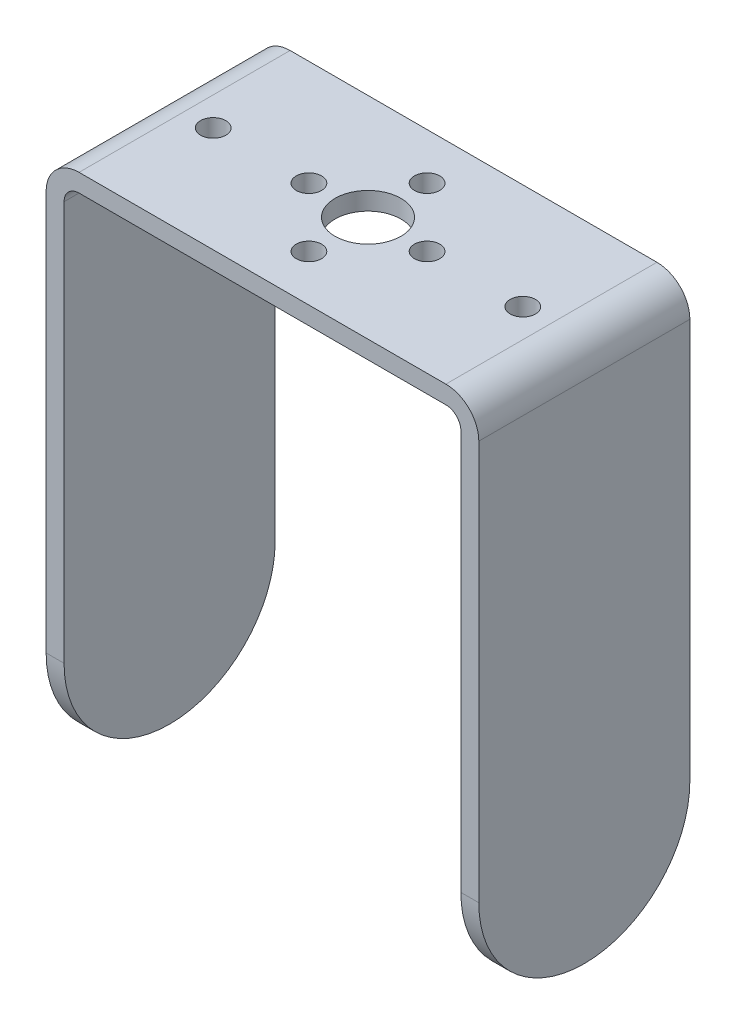
SolidWorks part; units mm, degrees
ref_plane "Front Plane" through (0, 0, 0) normal (0, 0, 1) x (1, 0, 0)
ref_plane "Top Plane" through (0, 0, 0) normal (0, 1, 0) x (1, 0, 0)
ref_plane "Right Plane" through (0, 0, 0) normal (1, 0, 0) x (0, 0, -1)
sketch "Sketch1" plane through (0, 0, 0) normal (0, 0, 1) x (1, 0, 0)
  line L0 (-26.035, -64.77) -> (-26.035, -3.9624)
  line L1 (-22.0726, 0) -> (22.0726, 0)
  line L2 (26.035, -3.9624) -> (26.035, -64.77)
  arc A0 (22.0726, 0) -> (26.035, -3.9624) centre (22.0726, -3.9624) cw
  arc A1 (-26.035, -3.9624) -> (-22.0726, 0) centre (-22.0726, -3.9624) cw
  point P7 (26.035, 0)
  point P10 (-26.035, 0)
  dimension "D3" = 3.9624
  dimension "D1" = 52.07
  dimension "D2" = 64.77
extrude "Extrude-Thin1" add sketch "Sketch1" along normal mid plane 25.4 thin thin type one direction wall 2.159
fillet "Fillet1" radius 12.7 4 edges at (24.9555, -64.77, -12.7) (24.9555, -64.77, 12.7) (-24.9555, -64.77, -12.7) (-24.9555, -64.77, 12.7)
sketch "Sketch2" plane through (0, 0, 0) normal (0, 1, 0) x (1, 0, 0)
  circle A0 centre (0, 0) radius 3.9624
  dimension "D1" = 7.9248
extrude "Cut-Extrude1" cut sketch "Sketch2" against normal through all
hole_wizard "#31 (0.12) Diameter Hole1" positions "Sketch3" profile "Sketch4" hole size "#31" standard "ANSI Inch" end condition through all
sketch "Sketch3" plane through (0, 0, 0) normal (0, 1, 0) x (1, 0, 0)
  line L0 (18.6309, 0) -> (-18.6309, 0) construction
  circle A0 centre (0, 0) radius 7.112 construction
  point P0 (0, -7.112)
  point P2 (0, 7.112)
  point P4 (-7.112, 0)
  point P6 (7.112, 0)
  point P8 (18.6309, 0)
  point P10 (-18.6309, 0)
  dimension "D1" = 14.224
  dimension "D2" = 37.2618
sketch "Sketch4" plane through (0, 0, 7.112) normal (1, 0, 0) x (0, 0, 1)
  line L0 (0, 0) -> (0, 64.77)
  line L1 (0, 64.77) -> (1.524, 64.77)
  line L2 (1.524, 64.77) -> (1.524, 0)
  line L5 (1.524, 0) -> (0, 0)
  line L11 (0, -6.35) -> (0, 107.95) construction
  dimension "Thru Hole Dia." = 3.048
  dimension "Thru Hole Depth" = 64.77
